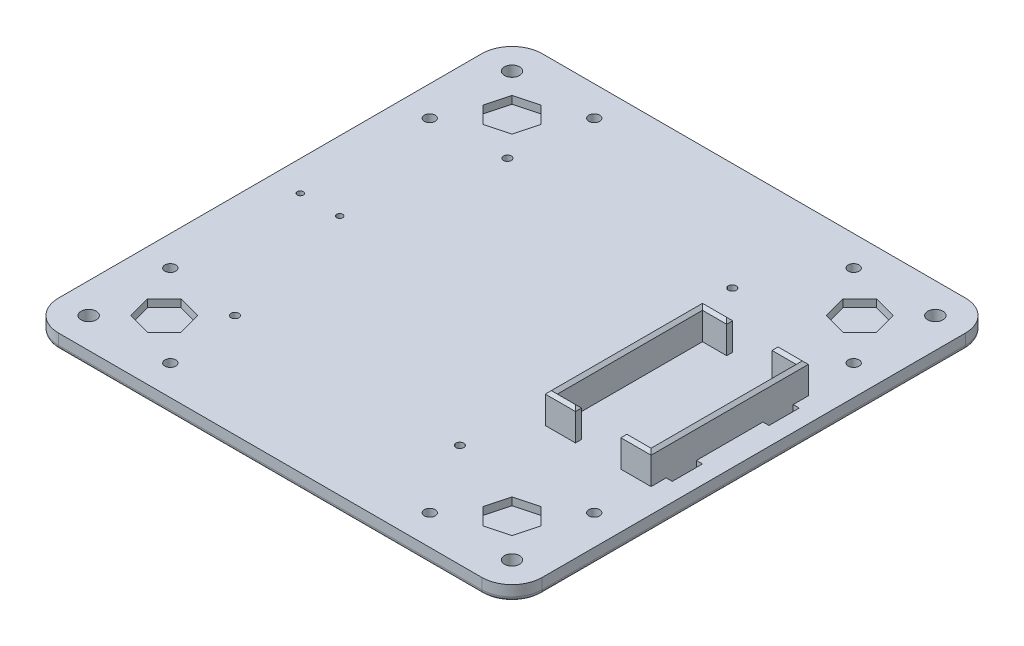
SolidWorks part; units mm, degrees
ref_plane "Front Plane" through (0, 0, 0) normal (0, 0, 1) x (1, 0, 0)
ref_plane "Top Plane" through (0, 0, 0) normal (0, 1, 0) x (1, 0, 0)
ref_plane "Right Plane" through (0, 0, 0) normal (1, 0, 0) x (0, 0, -1)
sketch "Sketch1" plane through (0, 0, 0) normal (0, 1, 0) x (1, 0, 0)
  line L1 (0, 0) -> (203.2, 0)
  line L2 (0, 0) -> (0, 203.2)
  line L3 (0, 203.2) -> (203.2, 203.2)
  line L4 (203.2, 0) -> (203.2, 203.2)
  dimension "D1" = 203.2
  dimension "D2" = 203.2
extrude "Boss-Extrude1" add sketch "Sketch1" along normal blind 6.35
fillet "Fillet1" radius 12.7 4 edges at (0, 3.175, -203.2) (0, 3.175, 0) (203.2, 3.175, 0) (203.2, 3.175, -203.2)
sketch "Sketch2" plane through (0, 0, 0) normal (0, -1, 0) x (1, 0, 0)
  circle A0 centre (12.7, -12.7) radius 3.175
  circle A1 centre (190.5, -12.7) radius 3.175
  circle A2 centre (190.5, -190.5) radius 3.175
  circle A3 centre (12.7, -190.5) radius 3.175
  arc A4 (190.5, -203.2) -> (203.2, -190.5) centre (190.5, -190.5) ccw construction
  arc A5 (12.7, 0) -> (0, -12.7) centre (12.7, -12.7) ccw construction
  dimension "D1" = 6.35
extrude "Cut-Extrude1" cut sketch "Sketch2" against normal through all
sketch "Sketch22" plane through (0, 6.35, 0) normal (0, 1, 0) x (1, 0, 0)
  line L17 (190.5, 203.2) -> (12.7, 203.2) construction
  line L18 (203.2, 12.7) -> (203.2, 190.5) construction
  line L21 (181.6542, 181.6542) -> (172.0521, 184.2271)
  line L22 (172.0521, 184.2271) -> (165.0229, 177.1979)
  line L23 (165.0229, 177.1979) -> (167.5958, 167.5958)
  line L24 (167.5958, 167.5958) -> (177.1979, 165.0229)
  line L25 (177.1979, 165.0229) -> (184.2271, 172.0521)
  line L26 (184.2271, 172.0521) -> (181.6542, 181.6542)
  line L27 (174.625, 174.625) -> (190.5, 190.5) construction
  line L28 (101.6, 203.2) -> (101.6, 0) construction
  line L29 (12.7, 0) -> (190.5, 0) construction
  line L30 (203.2, 101.6) -> (0, 101.6) construction
  line L31 (0, 190.5) -> (0, 12.7) construction
  line L32 (28.575, 174.625) -> (12.7, 190.5) construction
  line L33 (18.9729, 172.0521) -> (21.5458, 181.6542)
  line L34 (26.0021, 165.0229) -> (18.9729, 172.0521)
  line L35 (35.6042, 167.5958) -> (26.0021, 165.0229)
  line L36 (38.1771, 177.1979) -> (35.6042, 167.5958)
  line L37 (31.1479, 184.2271) -> (38.1771, 177.1979)
  line L38 (21.5458, 181.6542) -> (31.1479, 184.2271)
  line L39 (174.625, 28.575) -> (190.5, 12.7) construction
  line L40 (184.2271, 31.1479) -> (181.6542, 21.5458)
  line L41 (177.1979, 38.1771) -> (184.2271, 31.1479)
  line L42 (167.5958, 35.6042) -> (177.1979, 38.1771)
  line L43 (165.0229, 26.0021) -> (167.5958, 35.6042)
  line L44 (172.0521, 18.9729) -> (165.0229, 26.0021)
  line L45 (181.6542, 21.5458) -> (172.0521, 18.9729)
  line L46 (28.575, 28.575) -> (12.7, 12.7) construction
  line L47 (21.5458, 21.5458) -> (31.1479, 18.9729)
  line L48 (31.1479, 18.9729) -> (38.1771, 26.0021)
  line L49 (38.1771, 26.0021) -> (35.6042, 35.6042)
  line L50 (35.6042, 35.6042) -> (26.0021, 38.1771)
  line L51 (26.0021, 38.1771) -> (18.9729, 31.1479)
  line L52 (18.9729, 31.1479) -> (21.5458, 21.5458)
  circle A0 centre (174.625, 174.625) radius 8.609 construction
  circle A1 centre (28.575, 174.625) radius 8.609 construction
  circle A2 centre (174.625, 28.575) radius 8.609 construction
  circle A3 centre (28.575, 28.575) radius 8.609 construction
  dimension "D5" = 17.218
  dimension "D3" = 28.575
  dimension "D4" = 28.575
extrude "Cut-Extrude2" cut sketch "Sketch22" against normal blind 3.175
fillet "Fillet2" radius 1.905 12 edges at (3.7197, 0, -3.7197) (101.6, 0, 0) (199.4803, 0, -3.7197) (203.2, 0, -101.6) (199.4803, 0, -199.4803) (101.6, 0, -203.2) (3.7197, 0, -199.4803) (0, 0, -101.6) (12.7, 0, -15.875) (190.5, 0, -15.875) (190.5, 0, -193.675) (12.7, 0, -193.675)
sketch "Sketch28" plane through (0, 6.35, 0) normal (0, 1, 0) x (1, 0, 0)
  line L0 (190.5, 203.2) -> (12.7, 203.2) construction
  line L1 (203.2, 12.7) -> (203.2, 190.5) construction
  line L2 (12.7, 0) -> (190.5, 0) construction
  line L4 (0, 190.5) -> (0, 12.7) construction
  circle A0 centre (47.117, 190.627) radius 2.286
  circle A1 centre (156.083, 190.627) radius 2.286
  circle A2 centre (190.627, 156.083) radius 2.286
  circle A3 centre (190.627, 47.117) radius 2.286
  circle A4 centre (156.083, 12.573) radius 2.286
  circle A5 centre (47.117, 12.573) radius 2.286
  circle A6 centre (12.573, 156.083) radius 2.286
  circle A7 centre (12.573, 47.117) radius 2.286
  dimension "D4" = 4.572
  dimension "D1" = 12.573
  dimension "D2" = 12.573
  dimension "D3" = 12.573
  dimension "D5" = 12.573
  dimension "D6" = 47.117
  dimension "D7" = 47.117
  dimension "D8" = 47.117
  dimension "D9" = 47.117
extrude "Cut-Extrude3" cut sketch "Sketch28" against normal through all
sketch "Sketch29" plane through (0, 6.35, 0) normal (0, 1, 0) x (1, 0, 0)
  line L0 (40.64, 160.64) -> (40.64, 40.64) construction
  line L1 (40.64, 40.64) -> (140.64, 40.64) construction
  line L2 (140.64, 40.64) -> (140.64, 160.64) construction
  line L3 (140.64, 160.64) -> (40.64, 160.64) construction
  line L5 (12.7, 0) -> (190.5, 0) construction
  line L7 (151.13, 132.08) -> (161.29, 132.08)
  line L8 (151.13, 132.08) -> (151.13, 71.12)
  line L9 (151.13, 71.12) -> (161.29, 71.12)
  line L10 (190.5, 132.08) -> (190.5, 71.12)
  line L15 (193.04, 134.62) -> (193.04, 68.58)
  line L16 (148.59, 68.58) -> (161.29, 68.58)
  line L17 (148.59, 134.62) -> (148.59, 68.58)
  line L18 (148.59, 134.62) -> (161.29, 134.62)
  line L19 (203.2, 12.7) -> (203.2, 190.5) construction
  line L20 (0, 190.5) -> (0, 12.7) construction
  line L22 (161.29, 134.62) -> (161.29, 132.08)
  line L23 (180.34, 134.62) -> (180.34, 132.08)
  line L24 (180.34, 132.08) -> (190.5, 132.08)
  line L25 (151.13, 132.08) -> (190.5, 132.08) construction
  line L26 (180.34, 134.62) -> (193.04, 134.62)
  line L27 (148.59, 134.62) -> (193.04, 134.62) construction
  line L28 (161.29, 71.12) -> (161.29, 68.58)
  line L29 (180.34, 71.12) -> (180.34, 68.58)
  line L30 (180.34, 71.12) -> (190.5, 71.12)
  line L31 (151.13, 71.12) -> (190.5, 71.12) construction
  line L32 (180.34, 68.58) -> (193.04, 68.58)
  line L33 (148.59, 68.58) -> (193.04, 68.58) construction
  point P16 (193.04, 101.6)
  point P17 (203.2, 101.6)
  dimension "D1" = 100
  dimension "D2" = 120
  dimension "D3" = 40.64
  dimension "D4" = 60.96
  dimension "D5" = 39.37
  dimension "D6" = 2.54
  dimension "D7" = 10.16
  dimension "D8" = 40.64
  dimension "D9" = 12.7
  dimension "D10" = 12.7
  dimension "D11" = 12.7
  dimension "D12" = 12.7
extrude "Boss-Extrude2" add sketch "Sketch29" along normal blind 12.7
chamfer "Chamfer1" distance 1.27 angle 45 16 edges at (156.21, 19.05, -71.12) (161.29, 19.05, -69.85) (154.94, 19.05, -68.58) (148.59, 19.05, -101.6) (154.94, 19.05, -134.62) (161.29, 19.05, -133.35) (156.21, 19.05, -132.08) (151.13, 19.05, -101.6) (190.5, 19.05, -101.6) (185.42, 19.05, -132.08) (180.34, 19.05, -133.35) (186.69, 19.05, -134.62) (193.04, 19.05, -101.6) (186.69, 19.05, -68.58) (180.34, 19.05, -69.85) (185.42, 19.05, -71.12)
sketch "Sketch30" plane through (0, 6.35, 0) normal (0, 1, 0) x (1, 0, 0)
  line L0 (40.64, 160.64) -> (140.64, 160.64) construction
  line L1 (140.64, 160.64) -> (140.64, 40.64) construction
  line L2 (140.64, 40.64) -> (40.64, 40.64) construction
  line L3 (40.64, 40.64) -> (40.64, 160.64) construction
  line L5 (148.59, 134.62) -> (148.59, 68.58) construction
  line L6 (148.59, 128.27) -> (146.05, 128.27)
  line L7 (148.59, 128.27) -> (148.59, 115.57)
  line L8 (148.59, 115.57) -> (146.05, 115.57)
  line L9 (146.05, 128.27) -> (146.05, 115.57)
  line L10 (193.04, 134.62) -> (193.04, 68.58) construction
  line L11 (148.59, 74.93) -> (146.05, 74.93)
  line L12 (148.59, 74.93) -> (148.59, 87.63)
  line L13 (148.59, 87.63) -> (146.05, 87.63)
  line L14 (146.05, 74.93) -> (146.05, 87.63)
  line L15 (193.04, 74.93) -> (195.58, 74.93)
  line L16 (193.04, 74.93) -> (193.04, 87.63)
  line L17 (193.04, 87.63) -> (195.58, 87.63)
  line L18 (195.58, 74.93) -> (195.58, 87.63)
  line L19 (180.34, 134.62) -> (193.04, 134.62) construction
  line L20 (193.04, 128.27) -> (195.58, 128.27)
  line L21 (193.04, 128.27) -> (193.04, 115.57)
  line L22 (193.04, 115.57) -> (195.58, 115.57)
  line L23 (195.58, 128.27) -> (195.58, 115.57)
  line L24 (180.34, 68.58) -> (193.04, 68.58) construction
  circle A0 centre (43.4145, 157.8655) radius 1.651
  circle A1 centre (137.8655, 157.8655) radius 1.651
  circle A2 centre (137.8655, 43.4145) radius 1.651
  circle A3 centre (43.4145, 43.4145) radius 1.651
  point P36 (146.05, 81.28)
  point P37 (195.58, 81.28)
  point P38 (195.58, 121.92)
  point P39 (146.05, 121.92)
  dimension "D1" = 3.302
  dimension "D2" = 2.7745
  dimension "D3" = 2.7745
  dimension "D4" = 2.7745
  dimension "D5" = 2.7745
  dimension "D6" = 2.54
  dimension "D7" = 12.7
  dimension "D8" = 6.35
  dimension "D9" = 6.35
extrude "Cut-Extrude4" cut sketch "Sketch30" against normal through all
sketch "Sketch31" plane through (0, 6.35, 0) normal (0, 1, 0) x (1, 0, 0)
  line L0 (10.16, 104.14) -> (10.16, 76.2) construction
  line L1 (10.16, 76.2) -> (31.75, 76.2) construction
  line L2 (31.75, 76.2) -> (31.75, 104.14) construction
  line L3 (31.75, 104.14) -> (10.16, 104.14) construction
  line L4 (0, 190.5) -> (0, 12.7) construction
  line L5 (12.7, 0) -> (190.5, 0) construction
  line L6 (12.7, 101.6) -> (29.21, 101.6) construction
  circle A0 centre (12.7, 101.6) radius 1.27
  circle A1 centre (29.21, 101.6) radius 1.27
  point P12 (20.955, 101.6)
  point P13 (20.955, 104.14)
  dimension "D5" = 16.51
  dimension "D7" = 2.54
  dimension "D1" = 27.94
  dimension "D2" = 21.59
  dimension "D3" = 10.16
  dimension "D4" = 76.2
  dimension "D6" = 2.54
extrude "Cut-Extrude5" cut sketch "Sketch31" against normal through all
